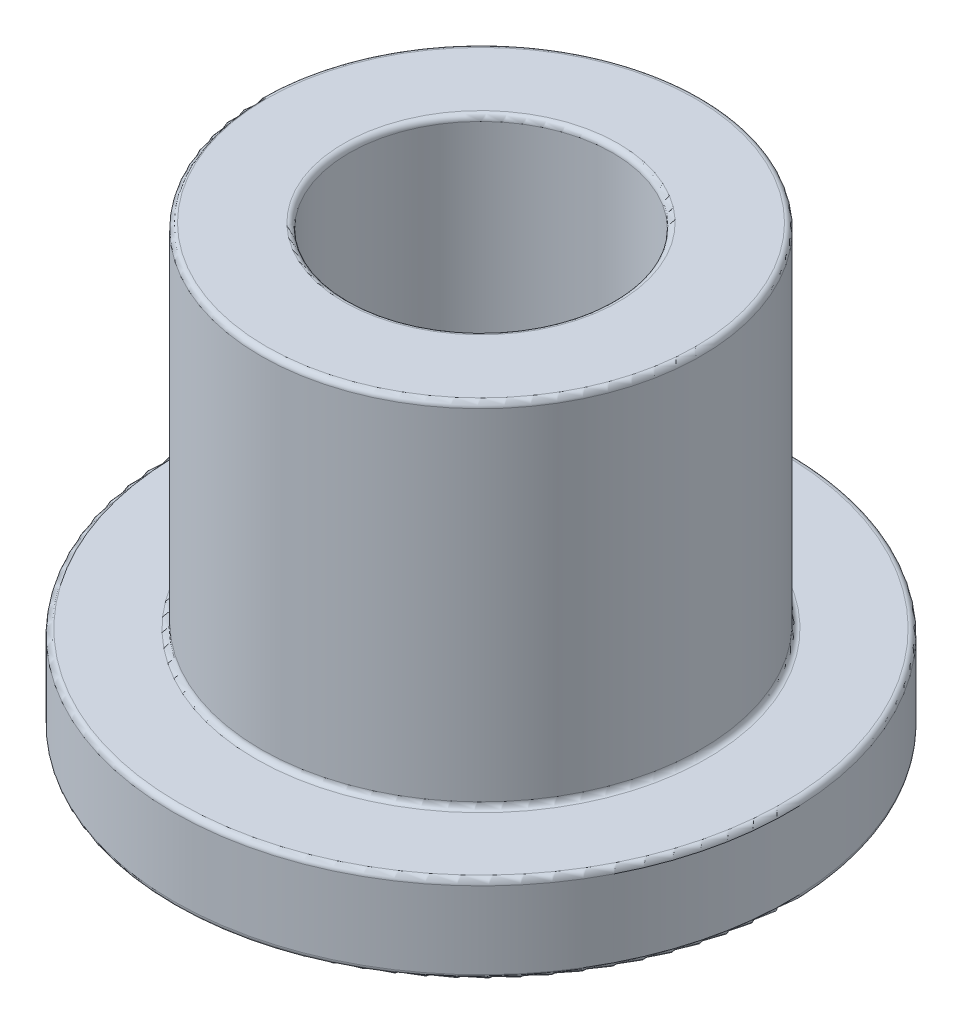
SolidWorks part; units mm, degrees
material "Commercial Bronze, UNS C22000 (90-10 Bronze)"
ref_plane "Front" through (0, 0, 0) normal (0, 0, 1) x (1, 0, 0)
ref_plane "Top" through (0, 0, 0) normal (0, 1, 0) x (1, 0, 0)
ref_plane "Right" through (0, 0, 0) normal (1, 0, 0) x (0, 0, -1)
sketch "Sketch1" plane through (0, 0, 0) normal (0, 1, 0) x (1, 0, 0)
  circle A0 centre (0, 0) radius 3
  circle A1 centre (0, 0) radius 5.01
  circle A2 centre (0, 0) radius 7
  dimension "ID" = 6
  dimension "OD" = 10.02
  dimension "FlangeOD" = 14
sketch "Sketch2" plane through (0, 0, 0) normal (1, 0, 0) x (0, 0, -1)
  line L0 (7, 0) -> (7, 2) construction
  line L1 (-5.01, 0) -> (-5.01, 10) construction
  line L8 (0, 0) -> (0, 10) construction
  point P5 (-7, 0)
  dimension "Flange Thickness" = 2
  dimension "Length" = 10
sketch "Sketch3" plane through (0, 0, 0) normal (0, 1, 0) x (1, 0, 0)
  circle A0 centre (0, 0) radius 3 construction
  circle A1 centre (0, 0) radius 5.01 construction
  circle A2 centre (0, 0) radius 3
  circle A3 centre (0, 0) radius 5.01
extrude "Boss-Extrude1" add sketch "Sketch3" along normal up to vertex (10 mm away) up to point (0, 10, 5.01)
sketch "Sketch4" plane through (0, 0, 0) normal (0, 1, 0) x (1, 0, 0)
  circle A0 centre (0, 0) radius 7 construction
  circle A1 centre (0, 0) radius 5.01 construction
  circle A2 centre (0, 0) radius 7
  circle A3 centre (0, 0) radius 5.01
extrude "Boss-Extrude2" add sketch "Sketch4" along normal up to vertex (2 mm away) up to point (0, 2, -7)
fillet "Fillet1" radius 0.125 6 edges at (0, 0, 3) (0, 0, 7) (0, 2, 5.01) (0, 2, 7) (0, 10, 3) (0, 10, 5.01)
